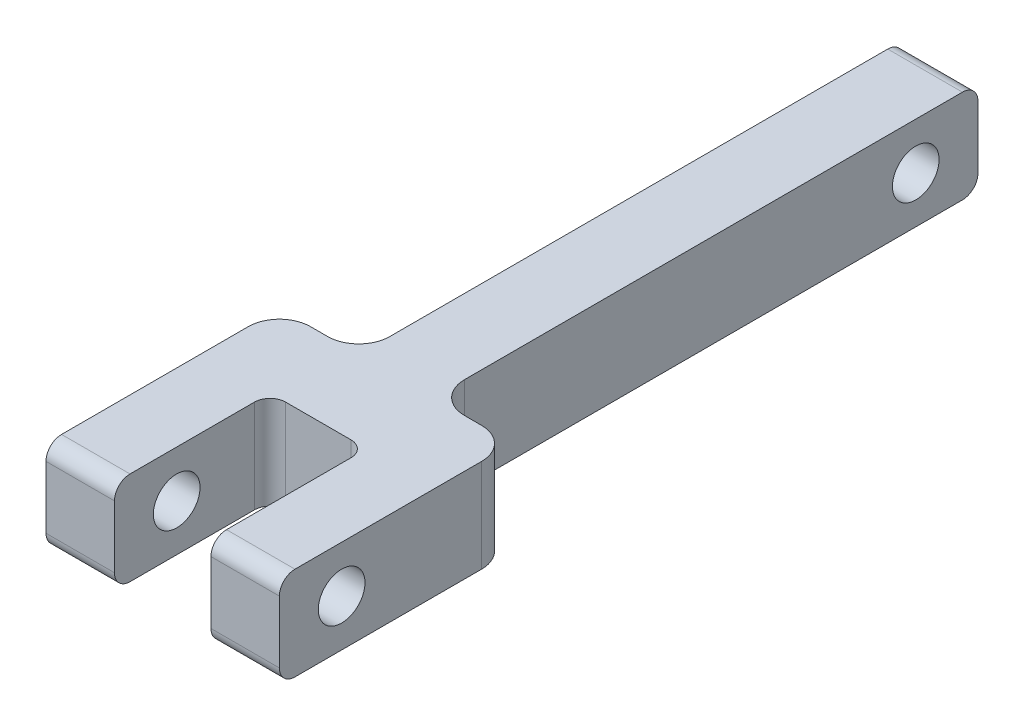
SolidWorks part; units mm, degrees
ref_plane "Alzado" through (0, 0, 0) normal (0, 0, 1) x (1, 0, 0)
ref_plane "Planta" through (0, 0, 0) normal (0, 1, 0) x (1, 0, 0)
ref_plane "Vista lateral" through (0, 0, 0) normal (1, 0, 0) x (0, 0, -1)
sketch "Croquis1" plane through (0, 0, 0) normal (1, 0, 0) x (0, 0, -1)
  line L0 (-24, 3) -> (24, 3)
  line L2 (-25, 0) -> (25, 0) construction
  line L3 (-25, 2) -> (-25, -2)
  line L4 (-24, -3) -> (24, -3)
  line L5 (25, 2) -> (25, -2)
  arc A0 (-25, -2) -> (-24, -3) centre (-24, -2) ccw
  arc A1 (-25, 2) -> (-24, 3) centre (-24, 2) cw
  arc A2 (24, -3) -> (25, -2) centre (24, -2) ccw
  arc A3 (24, 3) -> (25, 2) centre (24, 2) cw
  point P1 (0, 0)
  point P9 (-25, -3)
  point P13 (-25, 3)
  point P16 (25, -3)
  point P19 (25, 3)
  dimension "D3" = 1
  dimension "D4" = 1
  dimension "D1" = 3
  dimension "D2" = 50
extrude "Saliente-Extruir1" add sketch "Croquis1" along normal mid plane 4.8
sketch "Croquis2" plane through (0, 0, 0) normal (1, 0, 0) x (0, 0, -1)
  line L0 (-25, 2) -> (-25, -2) construction
  line L1 (25, -2) -> (25, 2) construction
  circle A0 centre (-21, 0) radius 1.5
  circle A1 centre (21, 0) radius 1.5
  dimension "D1" = 3
  dimension "D3" = 3
  dimension "D2" = 4
  dimension "D4" = 4
extrude "Cortar-Extruir1" cut sketch "Croquis2" against normal through all both and the other way through all
sketch "Croquis3" plane through (0, 0, 0) normal (1, 0, 0) x (0, 0, -1)
  line L0 (-25, 2) -> (-25, -2) construction
  line L1 (-25, 2) -> (-25, -2)
  line L2 (-24, 3) -> (-10, 3)
  line L3 (24, 3) -> (-24, 3) construction
  line L4 (-10, 3) -> (-10, -3)
  line L5 (-24, -3) -> (24, -3) construction
  line L6 (-10, -3) -> (-24, -3)
  circle A0 centre (-21, 0) radius 1.5 construction
  circle A1 centre (-21, 0) radius 1.5
  arc A2 (-24, 3) -> (-25, 2) centre (-24, 2) ccw construction
  arc A3 (-24, 3) -> (-25, 2) centre (-24, 2) ccw
  arc A4 (-25, -2) -> (-24, -3) centre (-24, -2) ccw construction
  arc A5 (-25, -2) -> (-24, -3) centre (-24, -2) ccw
  dimension "D1" = 15
extrude "Saliente-Extruir2" add sketch "Croquis3" along normal mid plane 15
sketch "Croquis4" plane through (0, 0, 0) normal (1, 0, 0) x (0, 0, -1)
  line L0 (-24, 3) -> (-15, 3)
  line L1 (-10, 3) -> (-24, 3) construction
  line L2 (-15, 3) -> (-15, -3)
  line L3 (-24, -3) -> (-10, -3) construction
  line L4 (-25, 2) -> (-25, -2)
  line L5 (-24, -3) -> (-10, -3)
  line L6 (-10, -3) -> (-10, 3)
  line L7 (-10, 3) -> (-24, 3)
  line L8 (-25, 2) -> (-25, -2)
  line L12 (-15, -3) -> (-24, -3)
  arc A2 (-24, 3) -> (-25, 2) centre (-24, 2) ccw
  arc A3 (-25, -2) -> (-24, -3) centre (-24, -2) ccw
  arc A4 (-24, 3) -> (-25, 2) centre (-24, 2) ccw
  arc A5 (-25, -2) -> (-24, -3) centre (-24, -2) ccw
  dimension "D2" = 10
  dimension "D1" = 0
extrude "Cortar-Extruir2" cut sketch "Croquis4" against normal mid plane 6.2
fillet "Redondeo1" radius 2 4 edges at (2.4, 0, 10) (-2.4, 0, 10) (7.5, 0, 10) (-7.5, 0, 10)
fillet "Redondeo2" radius 1 2 edges at (3.1, 0, 15) (-3.1, 0, 15)
